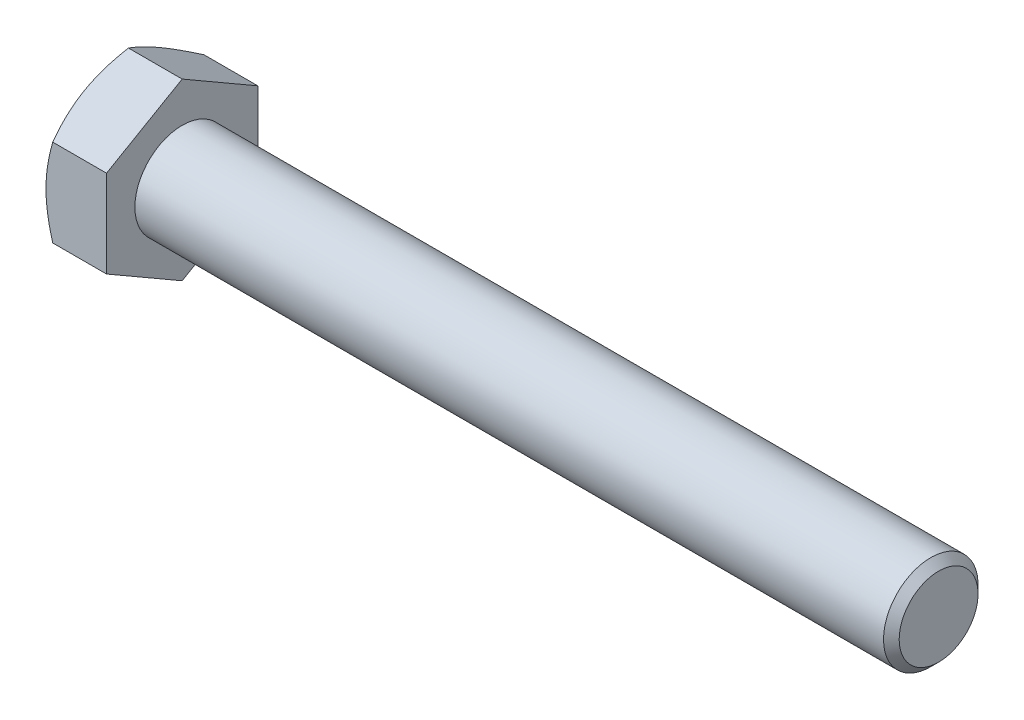
SolidWorks part; units mm, degrees
ref_plane "Front Plane" through (0, 0, 0) normal (0, 0, 1) x (1, 0, 0)
ref_plane "Top Plane" through (0, 0, 0) normal (0, 1, 0) x (1, 0, 0)
ref_plane "Right Plane" through (0, 0, 0) normal (1, 0, 0) x (0, 0, -1)
sketch "BaseHeadSke" plane through (0, 0, 0) normal (1, 0, 0) x (0, 0, -1)
  line L1 (0, 9.2376) -> (-8, 4.6188)
  line L2 (-8, 4.6188) -> (-8, -4.6188)
  line L3 (-8, -4.6188) -> (0, -9.2376)
  line L4 (0, -9.2376) -> (8, -4.6188)
  line L5 (8, -4.6188) -> (8, 4.6188)
  line L6 (8, 4.6188) -> (0, 9.2376)
  circle A0 centre (0, 0) radius 8 construction
extrude "BaseHead" add sketch "BaseHeadSke" along normal blind 6.4
sketch "HeadChamferSke" plane through (0, 0, 0) normal (0, 0, 1) x (1, 0, 0)
  line L0 (0, 0) -> (17.6355, 0) construction
  line L1 (0, 4.6188) -> (0, -4.6188) construction
  line L2 (0, 9.2376) -> (0, 8)
  line L3 (0, 8) -> (0.7145, 9.2376)
  line L4 (0.7145, 9.2376) -> (0, 9.2376)
  line L7 (6.4, 9.2376) -> (0, 9.2376) construction
  dimension "Angle_Chamfer_Head" = 30
revolve "HeadChamfer" cut sketch "HeadChamferSke" angle 360 about L0
sketch "BodySke" plane through (0, 0, 0) normal (0, 0, 1) x (1, 0, 0)
  line L0 (0, 0) -> (92.9385, 0) construction
  line L1 (0, 0) -> (0, 5)
  line L2 (0, 5) -> (85.572, 5)
  line L3 (85.572, 5) -> (86.4, 4.172)
  line L4 (86.4, 4.172) -> (86.4, 0)
  line L5 (86.4, 0) -> (0, 0)
  line L6 (6.4, 4.6188) -> (6.4, -4.6188) construction
  line L7 (7.9, 0) -> (7.9, 8.0817) construction
  dimension "Thread_minor" = 8.344
  dimension "Advance" = 1.5
revolve "BaseBody" add sketch "BodySke" angle 360 about L0
cosmetic thread "ThreadCosmetic" [suppressed] parameters "Thread_minor"=8.344
sketch "BearingFaceSke" plane through (0, 0, 0) normal (0, 0, 1) x (1, 0, 0)
  line L0 (0, 0) -> (95.3653, 0) construction
  line L1 (6.4, 9.2376) -> (6.4, 4.6188) construction
  line L2 (6.4, 8) -> (5.8, 8)
  line L3 (6.4, 8) -> (6.4, 18)
  line L4 (6.4, 18) -> (5.8, 18)
  line L5 (5.8, 8) -> (5.8, 18)
  dimension "D1" = 10
  dimension "D2" = 16
revolve "BearingFace" [suppressed] cut sketch "BearingFaceSke" angle 360 about L0
fillet "HeadFillet" [suppressed] radius 0.4
sketch "ThdSchSke" plane through (0, 0, 0) normal (0, 0, 1) x (1, 0, 0)
  line L0 (0, 0) -> (95.762, 0) construction
  line L1 (84.072, 5.9561) -> (84.072, 5)
  line L2 (84.072, 5.9561) -> (85.0281, 5.9561)
  line L3 (85.0281, 5.9561) -> (85.0281, 5)
  line L4 (85.0281, 5) -> (84.55, 4.172)
  line L5 (84.55, 4.172) -> (84.072, 5)
  dimension "D1" = 1.5
revolve "ThreadSchematic" [suppressed] cut sketch "ThdSchSke" angle 360 about L0
pattern_linear "ThdSchPat" [suppressed] of bodies 117
equation "\"Thread_minor@ThreadCosmetic\" = \"Thread_minor@BodySke\""
equation "\"D2@BearingFaceSke\" = \"Width_flats@BaseHeadSke\""
equation "\"D1@ThdSchSke\" = \"Advance@BodySke\""
equation "\"Advance@ThdSchPat\" = \"Advance@BodySke\""
equation "\"Tooth_Num@ThdSchPat\" =  int( \"Length@BodySke\" / \"Advance@BodySke\" ) - 1 "
